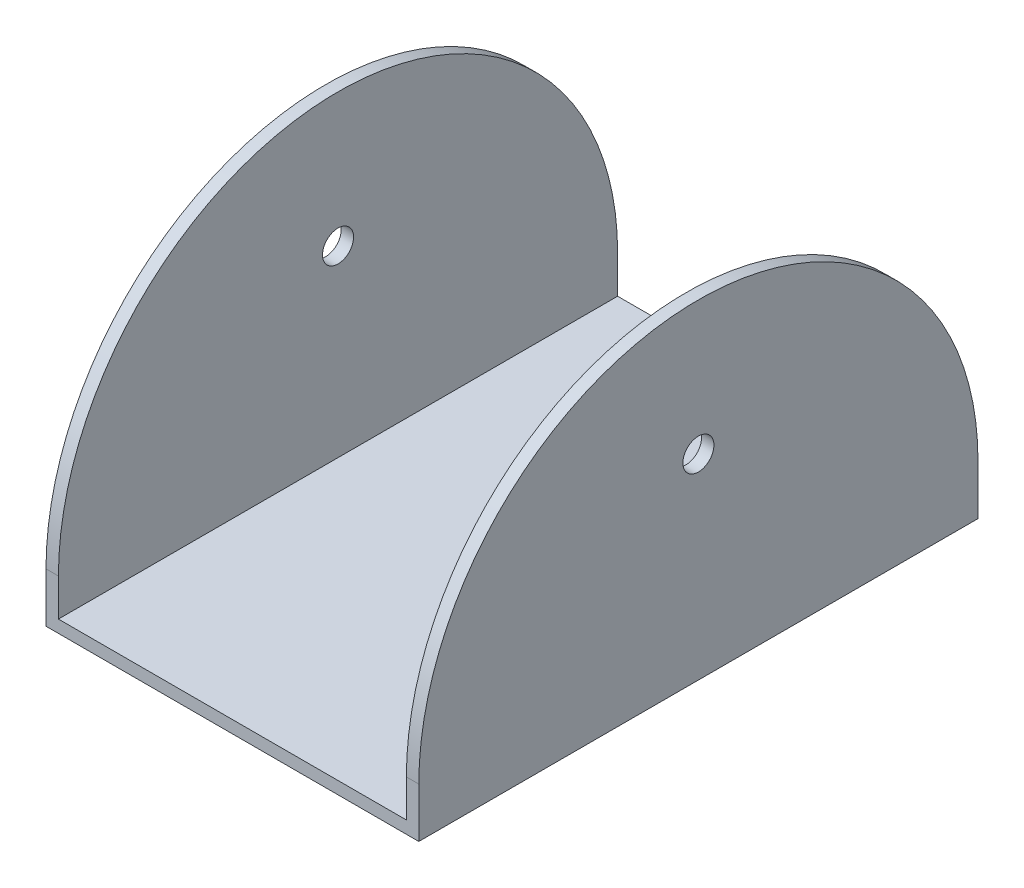
SolidWorks part; units mm, degrees
ref_plane "前视基准面" through (0, 0, 0) normal (0, 0, 1) x (1, 0, 0)
ref_plane "上视基准面" through (0, 0, 0) normal (0, 1, 0) x (1, 0, 0)
ref_plane "右视基准面" through (0, 0, 0) normal (1, 0, 0) x (0, 0, -1)
sketch "草图1" plane through (0, 0, 0) normal (0, 0, 1) x (1, 0, 0)
  line L0 (0, 11.905) -> (0, -9.2981) construction
  line L1 (30, -4.9835) -> (-30, -4.9835)
  line L2 (-30, -4.9835) -> (-30, 48.0165)
  line L3 (-30, 48.0165) -> (-28, 48.0165)
  line L4 (-28, 48.0165) -> (-28, -2.9835)
  line L5 (-28, -2.9835) -> (28, -2.9835)
  line L7 (28, 48.0165) -> (28, -2.9835)
  line L8 (30, 48.0165) -> (28, 48.0165)
  line L9 (30, -4.9835) -> (30, 48.0165)
  point P10 (0, -2.9835)
  point P13 (0, -4.9835)
  dimension "D1" = 2
  dimension "D2" = 2
  dimension "D3" = 53
  dimension "D4" = 60
extrude "凸台-拉伸1" add sketch "草图1" along normal blind 45 and the other way blind 45
sketch "草图3" plane through (30, 0, 0) normal (1, 0, 0) x (0, 0, -1)
  line L0 (-45, -4.9835) -> (-45, 48.0165) construction
  line L1 (45, -4.9835) -> (45, 48.0165) construction
  line L2 (45, 48.0165) -> (-45, 48.0165) construction
  line L3 (-45, 3.0165) -> (-45, 48.0165)
  line L4 (-45, 48.0165) -> (45, 48.0165)
  line L5 (45, 48.0165) -> (45, 3.0165)
  arc A0 (-45, 3.0165) -> (45, 3.0165) centre (0, 3.0165) cw
  line M1 (45, 48.0165) -> (-45, 48.0165)
  line M2 (-45, 48.0165) -> (-45, -4.9835)
  line M4 (45, -4.9835) -> (45, 48.0165)
extrude "切除-拉伸1" cut sketch "草图3" against normal through all contours A0 L4 M2 | A0 M1 M4 region at (30, 37.9649, -34.9484) region at (30, 37.9649, 34.9484)
sketch "草图4" plane through (-30, 0, 0) normal (-1, 0, 0) x (0, 0, 1)
  line L0 (0, 0) -> (0, 34.3471) construction
  line L1 (-45, -4.9835) -> (45, -4.9835) construction
  circle A0 centre (0, 26.5165) radius 2.5
  dimension "D1" = 5
  dimension "D2" = 31.5
extrude "切除-拉伸2" cut sketch "草图4" against normal through all
sketch "草图5" plane through (0, -4.9835, 0) normal (0, -1, 0) x (1, 0, 0)
  line L0 (0, 45) -> (0, -45) construction
  line L1 (-30, 45) -> (30, 45) construction
  line L2 (-30, -45) -> (30, -45) construction
  line L3 (-30, 0) -> (30, 0) construction
  line L4 (-30, -45) -> (-30, 45) construction
  line L5 (30, -45) -> (30, 45) construction
  circle A0 centre (0, 0) radius 4
  dimension "D1" = 8
extrude "切除-拉伸3" cut sketch "草图5" against normal blind 50
